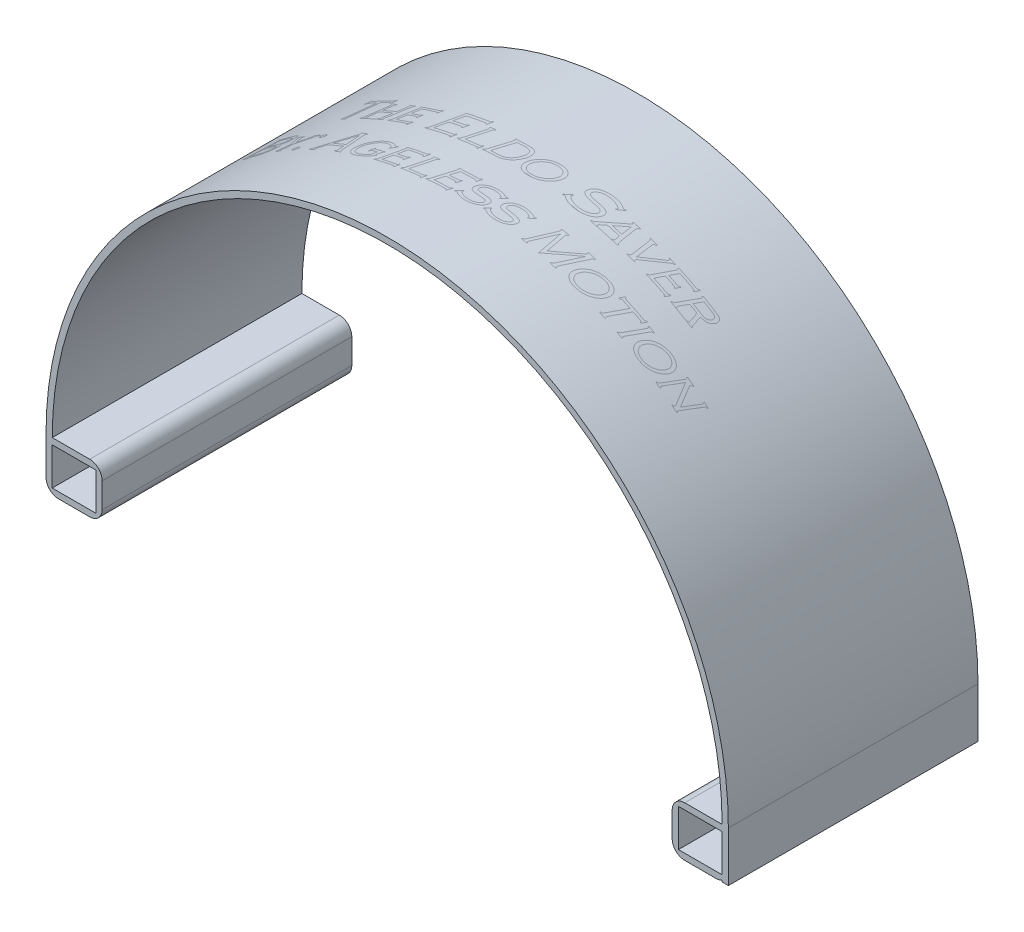
SolidWorks part; units mm, degrees
material "Nylon 6/10"
ref_plane "Front Plane" through (0, 0, 0) normal (0, 0, 1) x (1, 0, 0)
ref_plane "Top Plane" through (0, 0, 0) normal (0, 1, 0) x (1, 0, 0)
ref_plane "Right Plane" through (0, 0, 0) normal (1, 0, 0) x (0, 0, -1)
sketch "Sketch1" plane through (0, 0, 0) normal (0, 0, 1) x (1, 0, 0)
  line L0 (-80.5, 0) -> (80.5, 0) construction
  line L1 (-80.5, 0) -> (-82, 0)
  line L2 (80.5, 0) -> (82, 0)
  arc A0 (80.5, 0) -> (-80.5, 0) centre (0, 0) ccw
  arc A1 (82, 0) -> (-82, 0) centre (0, 0) ccw
  dimension "D1" = 80.5
  dimension "D2" = 1.5
extrude "Boss-Extrude2" add sketch "Sketch1" along normal mid plane 60
ref_plane "Plane1" through (0, 150, 0) normal (0, 1, 0) x (1, 0, 0)
sketch "Sketch3" plane through (0, 150, 0) normal (0, 1, 0) x (1, 0, 0)
  line L0 (-115.5974, 0) -> (115.5974, 0)
  text T0 "<i>The Eldo Saver</i>\r\n<i>By: Ageless Motion</i>" font "Copperplate Gothic Light" height in points 36
  point P4 (0, 0)
wrap "Wrap1" sketch "Sketch3" wrap type scribe source sketch "Sketch3" face at (0, 41, 0)
sketch "Sketch4" plane through (0, 0, 0) normal (0, -1, 0) x (1, 0, 0)
  line L1 (-82, 30) -> (-80.5, 30)
  line L2 (-82, 30) -> (-82, -30)
  line L3 (-82, -30) -> (-80.5, -30)
  line L4 (-80.5, 30) -> (-80.5, -30)
  line L5 (80.5, 30) -> (82, 30)
  line L6 (80.5, 30) -> (80.5, -30)
  line L7 (80.5, -30) -> (82, -30)
  line L8 (82, 30) -> (82, -30)
extrude "Boss-Extrude3" add sketch "Sketch4" along normal blind 12
sketch "Sketch5" plane through (80.5, 0, 0) normal (-1, 0, 0) x (0, 0, 1)
  line L0 (30, -12) -> (30, 0) construction
  line L1 (-30, -12) -> (30, -12)
  line L2 (-30, -12) -> (-30, -10.5)
  line L3 (-30, -10.5) -> (30, -10.5)
  line L4 (30, -12) -> (30, -10.5)
  dimension "D1" = 1.5
extrude "Boss-Extrude4" add sketch "Sketch5" along normal blind 12
sketch "Sketch6" plane through (0, -10.5, 0) normal (0, 1, 0) x (1, 0, 0)
  line L0 (-82, -30) -> (82, -30) construction
  line L1 (68.5, 30) -> (70, 30)
  line L2 (68.5, 30) -> (68.5, -30)
  line L3 (68.5, -30) -> (70, -30)
  line L4 (70, 30) -> (70, -30)
  dimension "D1" = 1.5
extrude "Boss-Extrude5" add sketch "Sketch6" along normal blind 10.5
sketch "Sketch9" plane through (70, 0, 0) normal (1, 0, 0) x (0, 0, -1)
  line L0 (30, -12) -> (30, 0) construction
  line L1 (-30, 0) -> (30, 0)
  line L2 (-30, 0) -> (-30, -1.5)
  line L3 (-30, -1.5) -> (30, -1.5)
  line L4 (30, 0) -> (30, -1.5)
  dimension "D1" = 1.5
extrude "Boss-Extrude6" add sketch "Sketch9" along normal up to next
fillet "Fillet1" radius 3 3 edges at (68.5, -12, 0) (82, -12, 0) (68.5, 0, 0)
mirror "Mirror11" about plane through (0, 0, 0) normal (1, 0, 0) of "Boss-Extrude3", "Boss-Extrude4", "Boss-Extrude5", "Boss-Extrude6"
fillet "Fillet3" radius 3 3 edges at (-82, -12, 0) (-68.5, -12, 0) (-68.5, 0, 0)
equation "\"userHeight\"= 1610mm"
equation "\"velcro_inner_radius\"= \"userHeight\" / 20'velcro inner radius"
equation "\"D1@Sketch1\"=\"velcro_inner_radius\""
